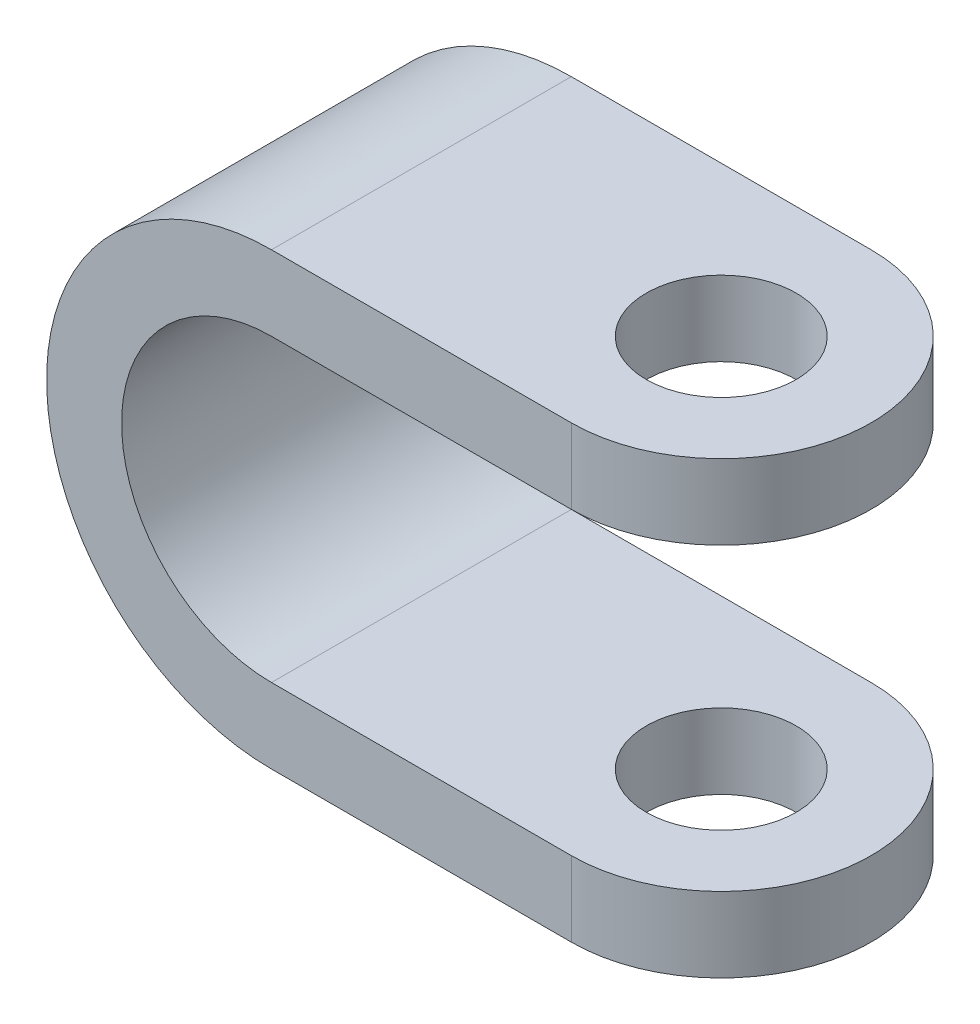
SolidWorks part; units mm, degrees
ref_plane "Front Plane" through (0, 0, 0) normal (0, 0, 1) x (1, 0, 0)
ref_plane "Top Plane" through (0, 0, 0) normal (0, 1, 0) x (1, 0, 0)
ref_plane "Right Plane" through (0, 0, 0) normal (1, 0, 0) x (0, 0, -1)
sketch "Sketch3" plane through (0, 0, 0) normal (0, 0, 1) x (1, 0, 0)
  line L1 (0, -15) -> (-60, -15)
  line L2 (-60, -55) -> (0, -55)
  arc A0 (-60, -15) -> (-60, -55) centre (-60, -35) ccw
  dimension "D3" = 20
  dimension "D1" = 15
  dimension "D2" = 60
extrude "Extrude-Thin1" add sketch "Sketch3" along normal blind 90 thin thin type one direction wall 10
sketch "Sketch4" plane through (0, 0, 0) normal (0, 1, 0) x (1, 0, 0)
  line L0 (-90, -25) -> (-90, -65)
  line L1 (-90, 0) -> (-90, -90) construction
  line L2 (-90, -25) -> (-20, -25)
  line L3 (-90, -65) -> (-20, -65)
  line L4 (0, -90) -> (0, 0) construction
  arc A0 (-20, -25) -> (-20, -65) centre (-20, -45) cw
  circle A1 centre (-20, -45) radius 10
  dimension "D2" = 20
  dimension "D1" = 40
  dimension "D3" = 25
extrude "Boss-Extrude1" add sketch "Sketch4" against normal blind 90 separate body
combine bodies "Combine2" operation type common bodies to combine 101 102
